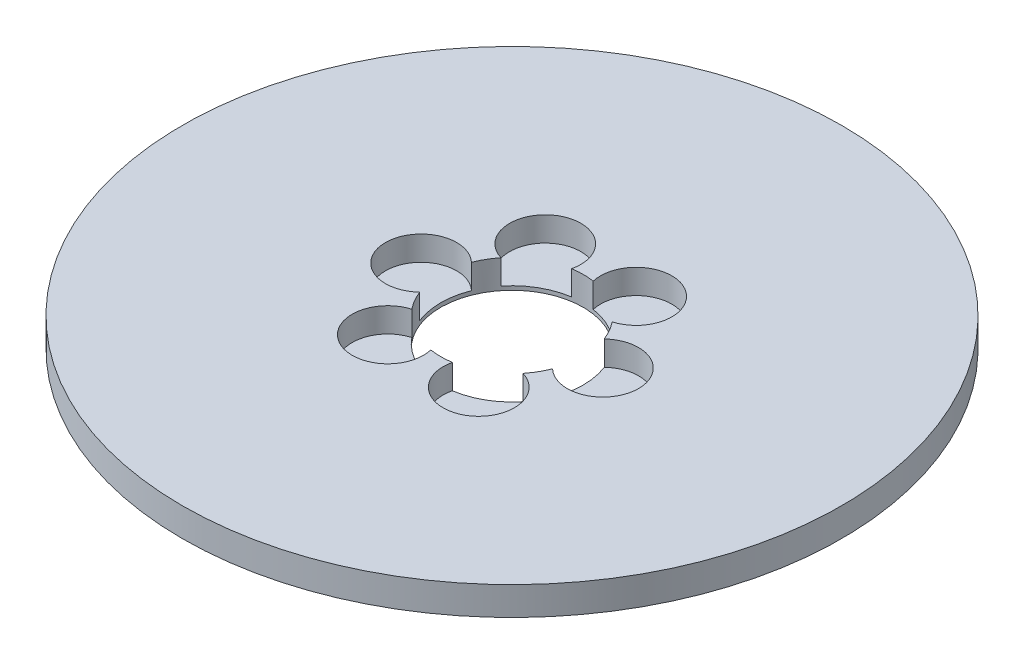
SolidWorks part; units mm, degrees
ref_plane "Front Plane" through (0, 0, 0) normal (0, 0, 1) x (1, 0, 0)
ref_plane "Top Plane" through (0, 0, 0) normal (0, 1, 0) x (1, 0, 0)
ref_plane "Right Plane" through (0, 0, 0) normal (1, 0, 0) x (0, 0, -1)
sketch "Sketch1" plane through (0, 0, 0) normal (0, 1, 0) x (1, 0, 0)
  circle A0 centre (0, 0) radius 92.5
  dimension "FLANGE_OD" = 185
extrude "Boss-Extrude1" add sketch "Sketch1" along normal blind 8
sketch "Sketch2" plane through (0, 0, 0) normal (0, 1, 0) x (1, 0, 0)
  circle A0 centre (0, 0) radius 20
  dimension "BORE_D" = 40
extrude "Cut-Extrude1" cut sketch "Sketch2" along normal through all
sketch "Sketch3" plane through (0, 8, 0) normal (0, 1, 0) x (1, 0, 0)
  circle A0 centre (0, 0) radius 25.5161 construction
  circle A1 centre (-25.5161, 0) radius 10
  dimension "BOLT_D" = 20
  dimension "BOLT_PCD" = 51.0322
extrude "Cut-Extrude2" cut sketch "Sketch3" against normal blind 6.8854
pattern_circular "CirPattern1" count 6 over 360 about axis through (0, 0, 0) along (0, 1, 0) of "Cut-Extrude2"
